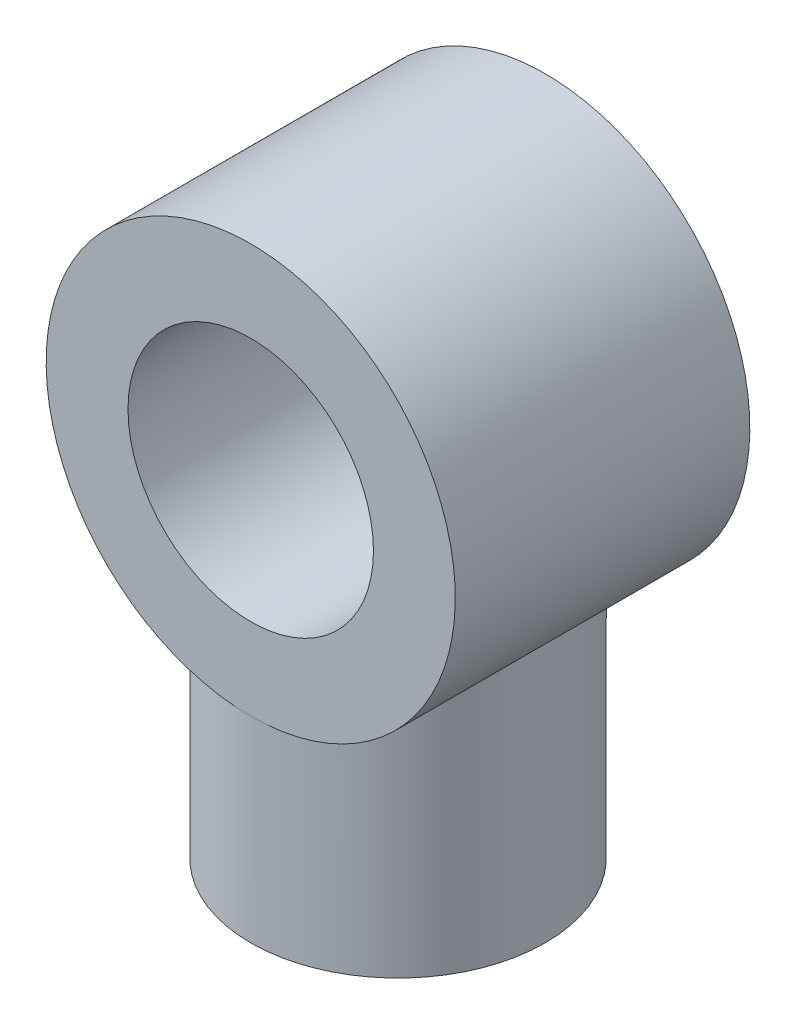
SolidWorks part; units mm, degrees
ref_plane "Front Plane" through (0, 0, 0) normal (0, 0, 1) x (1, 0, 0)
ref_plane "Top Plane" through (0, 0, 0) normal (0, 1, 0) x (1, 0, 0)
ref_plane "Right Plane" through (0, 0, 0) normal (1, 0, 0) x (0, 0, -1)
sketch "Sketch1" plane through (0, 0, 0) normal (0, 1, 0) x (1, 0, 0)
  circle A0 centre (0, 0) radius 6
  circle A1 centre (0, 0) radius 9
  dimension "D1" = 12
  dimension "D2" = 18
extrude "Boss-Extrude1" add sketch "Sketch1" along normal blind 12
sketch "Sketch3" plane through (0, 0, 0) normal (0, 0, 1) x (1, 0, 0)
  line L0 (9, 12) -> (-9, 12) construction
  circle A0 centre (0, 24.5) radius 7.5
  circle A1 centre (0, 24.5) radius 12.5
  point P3 (0.3441, 26.6091)
  dimension "D1" = 15
  dimension "D2" = 25
extrude "Boss-Extrude2" add sketch "Sketch3" along normal blind 9 and the other way blind 9 separate body
sketch "Sketch4" plane through (0, 12, 0) normal (0, 1, 0) x (1, 0, 0)
  circle A0 centre (0, 0) radius 9
  circle A1 centre (0, 0) radius 9 construction
extrude "Boss-Extrude3" add sketch "Sketch4" along normal up to surface up to face at (12.5, 24.5, -9)
thread "Thread1" pitch 1.25 method cut profile "Thread Profile3" start angle 0, offset 0, length 0, pitch 1.25, diameter 12
ref_plane "Plane3" through (6, 0, 0) normal (0, 0, 1) x (1, 0, 0)
sketch "Thread Profile3" plane through (6, 0, 0) normal (0, 0, 1) x (1, 0, 0)
  line L0 (0, 0) -> (0, 1.25) construction
  line L1 (0, 0) -> (0.6766, 0.3906)
  line L2 (0.6766, 0.3906) -> (0.6766, 0.5469)
  line L3 (0.6766, 0.5469) -> (0, 0.9375)
  line L4 (0.6766, 0.4687) -> (0, 0.4687) construction
  line L11 (0, 0) -> (0, 0.9375)
  point P2 (0, 0)
  dimension "Pitch" = 1.25
  dimension "Profile_Angle" = 60
  dimension "Profile_Land" = 0.1562
  dimension "Profile_Height" = 0.6766
